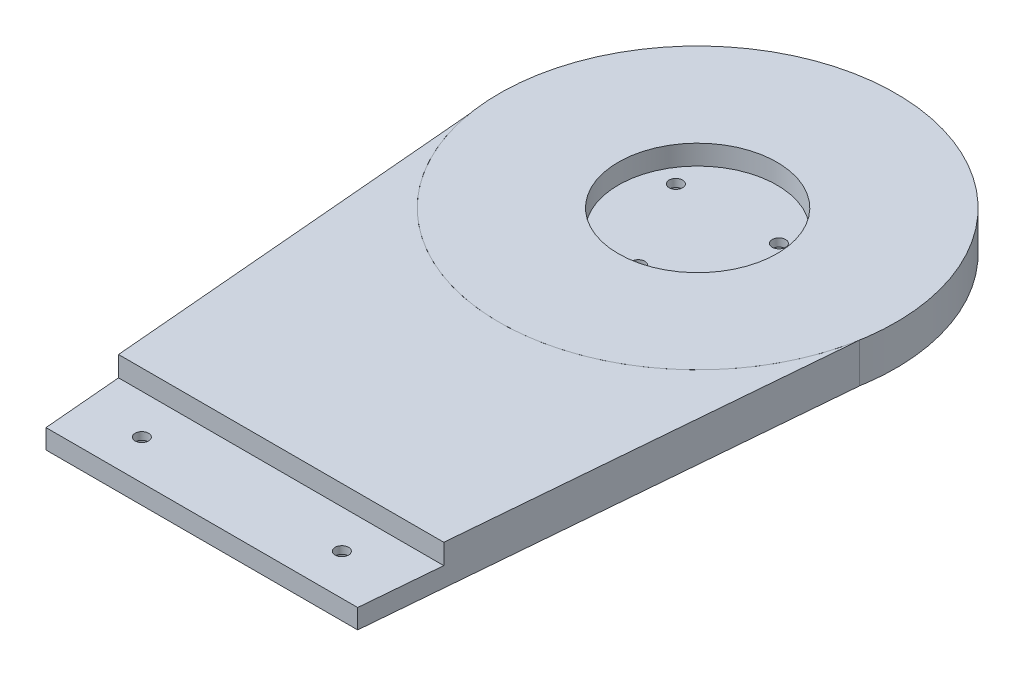
SolidWorks part; units mm, degrees
ref_plane "Front Plane" through (0, 0, 0) normal (0, 0, 1) x (1, 0, 0)
ref_plane "Top Plane" through (0, 0, 0) normal (0, 1, 0) x (1, 0, 0)
ref_plane "Right Plane" through (0, 0, 0) normal (1, 0, 0) x (0, 0, -1)
sketch "Sketch1" plane through (0, 0, 0) normal (0, 1, 0) x (1, 0, 0)
  circle A0 centre (0, 0) radius 50
extrude "Boss-Extrude1" add sketch "Sketch1" along normal blind 10
sketch "Sketch2" plane through (0, 10, 0) normal (0, 1, 0) x (1, 0, 0)
  circle A0 centre (0, 0) radius 20
extrude "Cut-Extrude1" cut sketch "Sketch2" against normal blind 5
sketch "Sketch7" plane through (0, 0, 0) normal (0, -1, 0) x (1, 0, 0)
  line L0 (10.1404, -5.8546) -> (10.1404, -9.1454)
  line L1 (0, 11.7091) -> (2.85, 13.3546)
  line L2 (2.85, 13.3546) -> (2.85, 16.6454)
  line L3 (2.85, 16.6454) -> (0, 18.2909)
  line L4 (0, 18.2909) -> (-2.85, 16.6454)
  line L5 (-2.85, 16.6454) -> (-2.85, 13.3546)
  line L6 (-2.85, 13.3546) -> (0, 11.7091)
  line L7 (10.1404, -9.1454) -> (12.9904, -10.7909)
  line L8 (12.9904, -10.7909) -> (15.8404, -9.1454)
  line L9 (15.8404, -9.1454) -> (15.8404, -5.8546)
  line L10 (15.8404, -5.8546) -> (12.9904, -4.2091)
  line L11 (12.9904, -4.2091) -> (10.1404, -5.8546)
  line L12 (-10.1404, -5.8546) -> (-12.9904, -4.2091)
  line L13 (-12.9904, -4.2091) -> (-15.8404, -5.8546)
  line L14 (-15.8404, -5.8546) -> (-15.8404, -9.1454)
  line L15 (-15.8404, -9.1454) -> (-12.9904, -10.7909)
  line L16 (-12.9904, -10.7909) -> (-10.1404, -9.1454)
  line L17 (-10.1404, -9.1454) -> (-10.1404, -5.8546)
  circle A0 centre (0, 0) radius 15
  circle A1 centre (0, 15) radius 2.85 construction
  point P25 (0, 0)
  dimension "D1" = 3
extrude "Cut-Extrude6" cut sketch "Sketch7" against normal blind 3 contours A0 L2 L3 L4 L5 | L2 A0 L5 L6 L1 | L13 L14 L15 L16 L17 L12 | L10 L11 L0 L7 L8 L9 region at (0, 0, 16.2315) region at (0, 0, 13.6745)
sketch "Sketch8" plane through (0, 0, 0) normal (0, -1, 0) x (1, 0, 0)
  line L0 (-2.85, 15) -> (2.85, 15) construction
  line L1 (-2.85, 16.6454) -> (-2.85, 13.3546) construction
  line L2 (2.85, 13.3546) -> (2.85, 16.6454) construction
  circle A0 centre (0, 15) radius 1.7
  circle A1 centre (12.9904, -7.5) radius 1.7
  circle A2 centre (-12.9904, -7.5) radius 1.7
  point P14 (0, 0)
  dimension "D1" = 3
extrude "Cut-Extrude7" cut sketch "Sketch8" against normal blind 10
sketch "Sketch9" plane through (0, 0, 0) normal (0, -1, 0) x (1, 0, 0)
  line L1 (-50, 0) -> (50, 0)
  line L2 (-50, 0) -> (-50, 350)
  line L3 (-50, 350) -> (50, 350)
  line L4 (50, 0) -> (50, 350)
  circle A0 centre (0, 0) radius 50 construction
  circle A1 centre (0, 0) radius 50
  circle M23 centre (0, 0) radius 50
  dimension "D1" = 350
extrude "Boss-Extrude3" add sketch "Sketch9" against normal blind 10 separate body contours L4 L3 L2 M23 region at (0, 0, 194.4346)
sketch "Sketch10" plane through (0, 0, 0) normal (0, -1, 0) x (1, 0, 0)
  line L0 (0, 350) -> (0, 0) construction
  line L1 (-50, 350) -> (50, 350) construction
  line L3 (-10.5, 299) -> (10.5, 299)
  line L4 (-10.5, 299) -> (-10.5, 340)
  line L5 (-10.5, 340) -> (10.5, 340)
  line L6 (10.5, 299) -> (10.5, 340)
  line L7 (-10.5, 299) -> (10.5, 340) construction
  line L8 (-10.5, 340) -> (10.5, 299) construction
  point P5 (0, 319.5)
  dimension "D1" = 41
  dimension "D2" = 21
  dimension "D3" = 10
extrude "Cut-Extrude8" cut sketch "Sketch10" against normal blind 10
sketch "Sketch11" plane through (0, 0, 0) normal (0, -1, 0) x (1, 0, 0)
  line L0 (-10.5, 340) -> (-10.5, 299) construction
  line L1 (-10.5, 292.5) -> (10.5, 292.5)
  line L2 (-10.5, 292.5) -> (-10.5, 346.5)
  line L3 (-10.5, 346.5) -> (10.5, 346.5)
  line L4 (10.5, 292.5) -> (10.5, 346.5)
  line L5 (-10.5, 292.5) -> (10.5, 346.5) construction
  line L6 (-10.5, 346.5) -> (10.5, 292.5) construction
  line L7 (-10.5, 340) -> (-10.5, 299)
  line L8 (10.5, 340) -> (-10.5, 340) construction
  line L9 (10.5, 340) -> (-10.5, 340)
  point P0 (0, 319.5)
  point P8 (-10.5, 319.5)
  point P9 (-10.5, 319.5)
  point P11 (0, 346.5)
  point P12 (0, 340)
  line M6 (10.5, 299) -> (-10.5, 299)
  line M8 (-10.5, 340) -> (10.5, 340)
  dimension "D1" = 54
  dimension "D2" = 21
extrude "Cut-Extrude9" cut sketch "Sketch11" against normal blind 1.5 contours L4 L3 L2 M8 | L1 L4 L2 M6 region at (0, 0, 295.75) region at (0, 0, 343.25)
sketch "Sketch12" plane through (0, 1.5, 0) normal (0, -1, 0) x (1, 0, 0)
  line L0 (-5, 343.75) -> (5, 343.75) construction
  line L1 (-10.5, 340) -> (10.5, 340) construction
  line L2 (-10.5, 346.5) -> (10.5, 346.5) construction
  line L3 (-10.5, 346.5) -> (10.5, 346.5)
  line L4 (-10.5, 319.5) -> (10.5, 319.5) construction
  line L5 (-10.5, 346.5) -> (-10.5, 292.5) construction
  line L6 (10.5, 292.5) -> (10.5, 346.5) construction
  circle A0 centre (-5, 343.75) radius 1.7
  circle A1 centre (5, 343.75) radius 1.7
  circle A2 centre (-5, 295.25) radius 1.7
  circle A3 centre (5, 295.25) radius 1.7
  point P3 (0, 343.75)
  point P9 (0, 346.5)
  dimension "D1" = 3.75
extrude "Cut-Extrude10" cut sketch "Sketch12" against normal blind 9 contours A0 | A1 | A2 | A3 region at (-5, 1.5, 343.75)
sketch "Sketch13" plane through (0, 0, 0) normal (0, -1, 0) x (1, 0, 0)
  line L0 (-50, 0) -> (-20, 350)
  line L1 (0, 350) -> (0, 0) construction
  line L2 (50, 0) -> (20, 350)
  line L3 (50, 0) -> (50, 350)
  line L4 (50, 350) -> (-50, 350)
  line L5 (-50, 350) -> (-50, 0)
  line L6 (50, 0) -> (50, 350)
  line L7 (50, 350) -> (-50, 350)
  line L8 (-50, 350) -> (-50, 0)
  arc A1 (50, 0) -> (-50, 0) centre (0, 0) ccw
  arc A2 (50, 0) -> (-50, 0) centre (0, 0) ccw
  arc M7 (-50, 0) -> (50, 0) centre (0, 0) cw
  line M8 (50, 0) -> (50, 350)
  line M9 (50, 350) -> (-50, 350)
  line M10 (-50, 350) -> (-50, 0)
  dimension "D2" = 20
  dimension "D1" = 0
extrude "Cut-Extrude11" cut sketch "Sketch13" against normal blind 10 contours L0 M7 M9 M10 | L2 M7 M8 M9 region at (-39.9981, 0, 233.3787) region at (39.9981, 0, 233.3787)
sketch "Sketch14" plane through (0, 0, 0) normal (0, -1, 0) x (1, 0, 0)
  line L0 (0, 0) -> (0, 125) construction
  line L2 (-64.1644, 125) -> (57.7014, 125)
  line L3 (-64.1644, 125) -> (-64.1644, 375)
  line L4 (-64.1644, 375) -> (57.7014, 375)
  line L5 (57.7014, 125) -> (57.7014, 375)
  dimension "D1" = 125
  dimension "D2" = 250
extrude "Cut-Extrude12" cut sketch "Sketch14" against normal blind 10
sketch "Sketch18" plane through (0, 10, 0) normal (0, 1, 0) x (1, 0, 0)
  line L0 (-41.2449, -105) -> (41, -105)
  line L1 (49.2707, -8.5089) -> (39.2857, -125) construction
  line L2 (-39.2857, -125) -> (39.2857, -125) construction
  line L3 (-25.1225, -115) -> (24.8775, -115) construction
  line L4 (-0.1225, -105) -> (0, -125) construction
  circle A0 centre (-25.1225, -115) radius 1.7
  circle A1 centre (24.9981, -114.6931) radius 1.7
  point P5 (-0.1225, -105)
  point P10 (-0.1225, -115)
  line M4 (-49.2707, -8.5089) -> (-39.2857, -125)
  line M5 (-39.2857, -125) -> (39.2857, -125)
  line M6 (39.2857, -125) -> (49.2707, -8.5089)
  dimension "D1" = 20
  dimension "D2" = 50
  dimension "D3" = 10
extrude "Cut-Extrude16" cut sketch "Sketch18" against normal blind 5.1 contours L0 A0 A1 M4 M5 M6 region at (0.0007, 10, 114.9298)
extrude "Cut-Extrude17" cut sketch "Sketch18<3>" against normal blind 10 contours A0 | A1
sketch "Sketch18<3>" plane through (0, 10, 0) normal (0, 1, 0) x (1, 0, 0) same geometry as "Sketch18"
sketch "Sketch19" plane through (0, 0, 0) normal (0, -1, 0) x (1, 0, 0)
  circle A0 centre (-25.1225, 115) radius 3
  circle A1 centre (24.9981, 114.6931) radius 3
extrude "Cut-Extrude18" cut sketch "Sketch19" against normal blind 3
